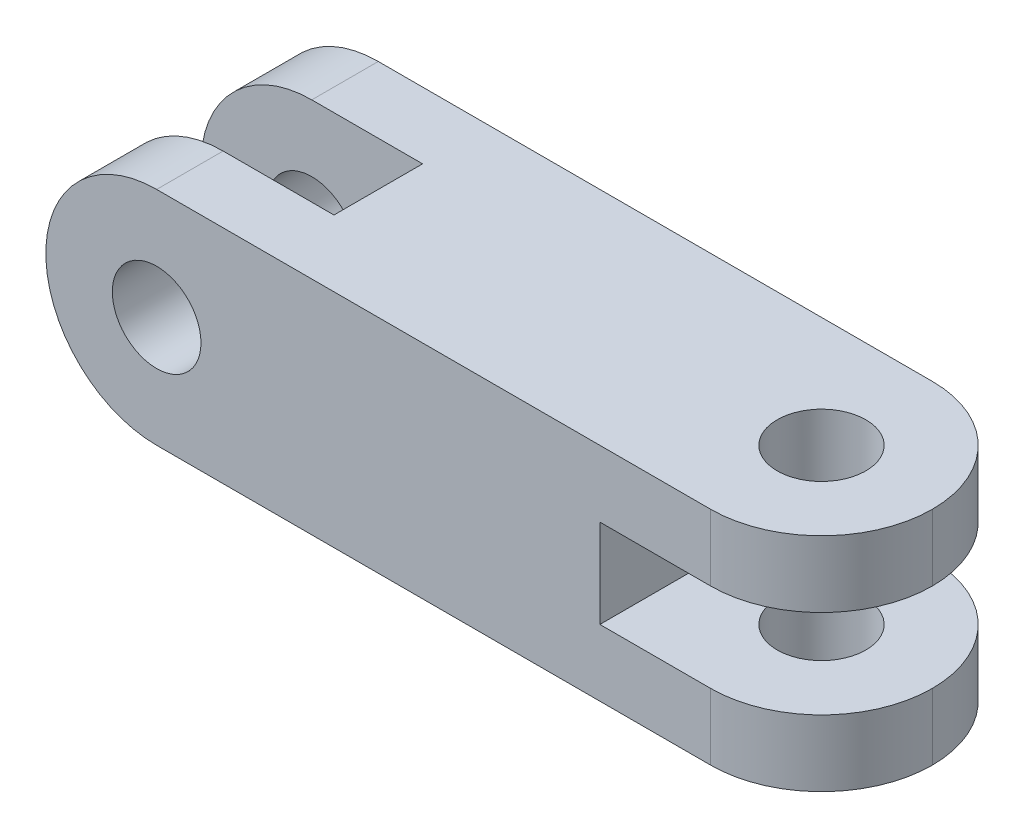
SolidWorks part; units mm, degrees
ref_plane "Front Plane" through (0, 0, 0) normal (0, 0, 1) x (1, 0, 0)
ref_plane "Top Plane" through (0, 0, 0) normal (0, 1, 0) x (1, 0, 0)
ref_plane "Right Plane" through (0, 0, 0) normal (1, 0, 0) x (0, 0, -1)
sketch "Sketch1" plane through (0, 0, 0) normal (0, 0, 1) x (1, 0, 0)
  line L0 (0, 0) -> (50000, 0) construction
  line L1 (0, 0) -> (0, 50000) construction
  line L2 (-150, 0) -> (0, 0) construction
  line L3 (-150, 25) -> (0, 25)
  line L4 (-150, -25) -> (0, -25)
  line L5 (0, 25) -> (0, -25)
  arc A0 (-150, 25) -> (-150, -25) centre (-150, 0) ccw
  point P7 (0, 0)
  dimension "D2" = 25
  dimension "D1" = 50
  dimension "D3" = 150
extrude "Boss-Extrude1" add sketch "Sketch1" along normal mid plane 50
fillet "Fillet1" radius 25 2 edges at (0, 0, -25) (0, 0, 25)
sketch "Sketch4" plane through (0, 25, 0) normal (0, 1, 0) x (1, 0, 0)
  line L0 (-25, 25) -> (-150, 25) construction
  line L1 (-186.2589, 10) -> (-125, 10)
  line L2 (-186.2589, 10) -> (-186.2589, -10)
  line L3 (-186.2589, -10) -> (-125, -10)
  line L4 (-125, 10) -> (-125, -10)
  line L5 (-175, 25) -> (-175, -25) construction
  dimension "D1" = 50
  dimension "D2" = 20
  dimension "D3" = 15
extrude "Cut-Extrude1" cut sketch "Sketch4" against normal blind 50 contours L1 L4 L3 L2
sketch "Sketch5" plane through (0, 0, -25) normal (0, 0, -1) x (-1, 0, 0)
  line L0 (25, 25) -> (150, 25) construction
  line L1 (-11.0749, 10) -> (50, 10)
  line L2 (-11.0749, 10) -> (-11.0749, -10)
  line L3 (-11.0749, -10) -> (50, -10)
  line L4 (50, 10) -> (50, -10)
  line L5 (0, 25) -> (0, -25) construction
  dimension "D1" = 20
  dimension "D2" = 15
  dimension "D3" = 50
extrude "Cut-Extrude2" cut sketch "Sketch5" against normal blind 50
hole_wizard "Ø20.0mm Dowel Hole1" positions "3DSketch2" profile "Sketch13" hole size "Ø20.0" standard "ISO" end condition through all
sketch3d "3DSketch2"
  line L0 (-150, 0, 25) -> (-150, 0, 10) construction
  line L1 (-25, -10, 0) -> (-25, -25, 0) construction
  point P0 (-150, 0, 25)
  point P4 (-25, -25, 0)
sketch "Sketch13" plane through (-150, 0, 25) normal (1, 0, 0) x (0, -1, 0)
  line L0 (0, 0) -> (0, 50)
  line L1 (0, 50) -> (10, 50)
  line L2 (10, 50) -> (10, 0)
  line L5 (10, 0) -> (0, 0)
  line L11 (0, -6.35) -> (0, 107.95) construction
  dimension "Thru Hole Dia." = 20
  dimension "Thru Hole Depth" = 50
